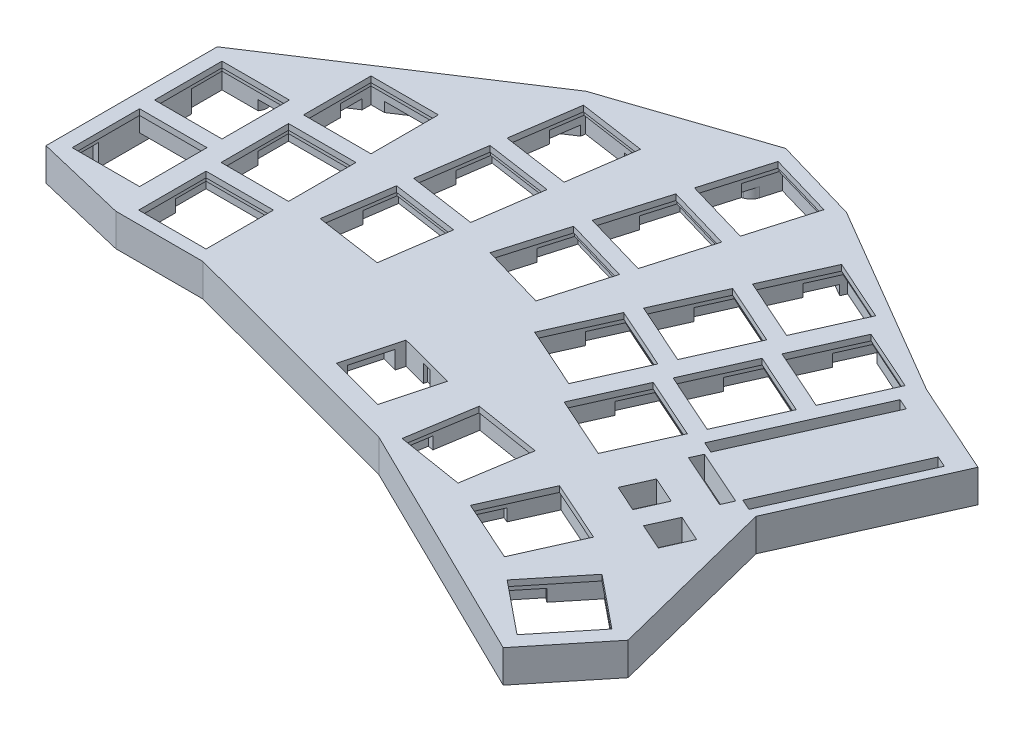
SolidWorks part; units mm, degrees
ref_plane "Front Plane" through (0, 0, 0) normal (0, 0, 1) x (1, 0, 0)
ref_plane "Top Plane" through (0, 0, 0) normal (0, 1, 0) x (1, 0, 0)
ref_plane "Right Plane" through (0, 0, 0) normal (1, 0, 0) x (0, 0, -1)
sketch "Ergogen Drawing" plane through (0, 0, 0) normal (0, 1, 0) x (1, 0, 0)
  line L0 (0.027, 17.9992) -> (18.027, 17.9992)
  line L1 (18.027, 17.9992) -> (18.027, -0.0008)
  line L2 (18.027, -0.0008) -> (0.027, -0.0008)
  line L3 (0.027, -0.0008) -> (0.027, 17.9992)
  line L4 (0.027, 34.9992) -> (18.027, 34.9992)
  line L5 (18.027, 34.9992) -> (18.027, 16.9992)
  line L6 (18.027, 16.9992) -> (0.027, 16.9992)
  line L7 (0.027, 16.9992) -> (0.027, 34.9992)
  line L8 (18.027, 15.9992) -> (36.027, 15.9992)
  line L9 (36.027, 15.9992) -> (36.027, -2.0008)
  line L10 (36.027, -2.0008) -> (18.027, -2.0008)
  line L11 (18.027, -2.0008) -> (18.027, 15.9992)
  line L12 (18.027, 32.9992) -> (36.027, 32.9992)
  line L13 (36.027, 32.9992) -> (36.027, 14.9992)
  line L14 (36.027, 14.9992) -> (18.027, 14.9992)
  line L15 (18.027, 14.9992) -> (18.027, 32.9992)
  line L16 (18.027, 49.9992) -> (36.027, 49.9992)
  line L17 (36.027, 49.9992) -> (36.027, 31.9992)
  line L18 (36.027, 31.9992) -> (18.027, 31.9992)
  line L19 (18.027, 31.9992) -> (18.027, 49.9992)
  line L20 (41.3768, 32.6051) -> (59.3329, 31.3495)
  line L21 (59.3329, 31.3495) -> (58.0773, 13.3933)
  line L22 (58.0773, 13.3933) -> (40.1211, 14.6489)
  line L23 (40.1211, 14.6489) -> (41.3768, 32.6051)
  line L24 (42.5626, 49.5637) -> (60.5188, 48.3081)
  line L25 (60.5188, 48.3081) -> (59.2631, 30.3519)
  line L26 (59.2631, 30.3519) -> (41.307, 31.6075)
  line L27 (41.307, 31.6075) -> (42.5626, 49.5637)
  line L28 (43.7485, 66.5223) -> (61.7046, 65.2667)
  line L29 (61.7046, 65.2667) -> (60.449, 47.3105)
  line L30 (60.449, 47.3105) -> (42.4929, 48.5661)
  line L31 (42.4929, 48.5661) -> (43.7485, 66.5223)
  line L32 (66.0898, 43.7082) -> (83.8507, 40.7838)
  line L33 (83.8507, 40.7838) -> (80.9263, 23.023)
  line L34 (80.9263, 23.023) -> (63.1655, 25.9473)
  line L35 (63.1655, 25.9473) -> (66.0898, 43.7082)
  line L36 (68.8517, 60.4823) -> (86.6126, 57.558)
  line L37 (86.6126, 57.558) -> (83.6882, 39.7971)
  line L38 (83.6882, 39.7971) -> (65.9274, 42.7215)
  line L39 (65.9274, 42.7215) -> (68.8517, 60.4823)
  line L40 (71.6136, 77.2565) -> (89.3745, 74.3321)
  line L41 (89.3745, 74.3321) -> (86.4501, 56.5713)
  line L42 (86.4501, 56.5713) -> (68.6893, 59.4956)
  line L43 (68.6893, 59.4956) -> (71.6136, 77.2565)
  line L44 (88.5581, 32.769) -> (105.9366, 28.0799)
  line L45 (105.9366, 28.0799) -> (101.2475, 10.7014)
  line L46 (101.2475, 10.7014) -> (83.869, 15.3905)
  line L47 (83.869, 15.3905) -> (88.5581, 32.769)
  line L48 (92.9866, 49.182) -> (110.3652, 44.4929)
  line L49 (110.3652, 44.4929) -> (105.6761, 27.1144)
  line L50 (105.6761, 27.1144) -> (88.2976, 31.8035)
  line L51 (88.2976, 31.8035) -> (92.9866, 49.182)
  line L52 (97.4152, 65.595) -> (114.7937, 60.906)
  line L53 (114.7937, 60.906) -> (110.1046, 43.5274)
  line L54 (110.1046, 43.5274) -> (92.7261, 48.2165)
  line L55 (92.7261, 48.2165) -> (97.4152, 65.595)
  line L56 (107.0448, 26.9674) -> (124.0477, 21.0597)
  line L57 (124.0477, 21.0597) -> (118.14, 4.0568)
  line L58 (118.14, 4.0568) -> (101.1371, 9.9645)
  line L59 (101.1371, 9.9645) -> (107.0448, 26.9674)
  line L60 (112.6243, 43.0257) -> (129.6273, 37.118)
  line L61 (129.6273, 37.118) -> (123.7195, 20.1151)
  line L62 (123.7195, 20.1151) -> (106.7166, 26.0228)
  line L63 (106.7166, 26.0228) -> (112.6243, 43.0257)
  line L64 (118.2039, 59.084) -> (135.2068, 53.1763)
  line L65 (135.2068, 53.1763) -> (129.299, 36.1734)
  line L66 (129.299, 36.1734) -> (112.2961, 42.0811)
  line L67 (112.2961, 42.0811) -> (118.2039, 59.084)
  line L68 (95.4197, 6.4051) -> (112.5714, 0.9445)
  line L69 (112.5714, 0.9445) -> (107.1108, -16.2072)
  line L70 (107.1108, -16.2072) -> (89.959, -10.7466)
  line L71 (89.959, -10.7466) -> (95.4197, 6.4051)
  line L72 (116.0129, -0.5249) -> (131.9353, -8.9198)
  line L73 (131.9353, -8.9198) -> (123.5404, -24.8423)
  line L74 (123.5404, -24.8423) -> (107.6179, -16.4473)
  line L75 (107.6179, -16.4473) -> (116.0129, -0.5249)
  line L76 (135.0644, -10.9721) -> (149.2602, -22.0392)
  line L77 (149.2602, -22.0392) -> (138.1931, -36.235)
  line L78 (138.1931, -36.235) -> (123.9973, -25.1679)
  line L79 (123.9973, -25.1679) -> (135.0644, -10.9721)
sketch "Layout Based on OG" plane through (0, 0, 0) normal (0, 1, 0) x (1, 0, 0)
  line L0 (0, 0) -> (0, 17) construction
  line L1 (0, 17) -> (18, 17) construction
  line L2 (18, 17) -> (18, 0) construction
  line L3 (18, 0) -> (0, 0) construction
  line L4 (2.05, 1.55) -> (2.05, 15.45)
  line L5 (2.05, 15.45) -> (15.95, 15.45)
  line L6 (15.95, 15.45) -> (15.95, 1.55)
  line L7 (15.95, 1.55) -> (2.05, 1.55)
  line L8 (109.1798, 58.6066) -> (27, -125.5436) construction
  line L9 (27, 46.7087) -> (27, -125.5436) construction
  line L10 (84.3863, 71.4039) -> (27, -125.5436) construction
  line L11 (54.2678, 62.3831) -> (27, -125.5436) construction
  line L12 (44.7261, 45.0233) -> (58.4821, 43.0274)
  line L13 (2.05, 18.55) -> (15.95, 18.55)
  line L14 (2.05, 18.55) -> (2.05, 32.45)
  line L15 (2.05, 32.45) -> (15.95, 32.45)
  line L16 (15.95, 18.55) -> (15.95, 32.45)
  line L17 (20.05, 31.2587) -> (33.95, 31.2587)
  line L18 (20.05, 31.2587) -> (20.05, 45.1587)
  line L19 (20.05, 45.1587) -> (33.95, 45.1587)
  line L20 (33.95, 31.2587) -> (33.95, 45.1587)
  line L21 (33.95, 28.1587) -> (20.05, 28.1587)
  line L22 (33.95, 28.1587) -> (33.95, 14.2587)
  line L23 (33.95, 14.2587) -> (20.05, 14.2587)
  line L24 (20.05, 28.1587) -> (20.05, 14.2587)
  line L25 (20.05, -2.7413) -> (33.95, -2.7413)
  line L26 (20.05, -2.7413) -> (20.05, 11.1587)
  line L27 (20.05, 11.1587) -> (33.95, 11.1587)
  line L28 (33.95, -2.7413) -> (33.95, 11.1587)
  line L29 (44.7261, 45.0233) -> (42.7302, 31.2674)
  line L30 (58.4821, 43.0274) -> (56.4861, 29.2714)
  line L31 (42.7302, 31.2674) -> (56.4861, 29.2714)
  line L32 (42.285, 28.1995) -> (56.041, 26.2036)
  line L33 (42.285, 28.1995) -> (40.2891, 14.4436)
  line L34 (56.041, 26.2036) -> (54.045, 12.4476)
  line L35 (40.2891, 14.4436) -> (54.045, 12.4476)
  line L36 (47.1672, 61.8472) -> (60.9232, 59.8512)
  line L37 (47.1672, 61.8472) -> (45.1712, 48.0912)
  line L38 (60.9232, 59.8512) -> (58.9272, 46.0953)
  line L39 (45.1712, 48.0912) -> (58.9272, 46.0953)
  line L40 (77.2802, 71.86) -> (90.6252, 67.9716)
  line L41 (77.2802, 71.86) -> (73.3917, 58.515)
  line L42 (90.6252, 67.9716) -> (86.7368, 54.6265)
  line L43 (73.3917, 58.515) -> (86.7368, 54.6265)
  line L44 (85.8695, 51.6503) -> (72.5245, 55.5388)
  line L45 (85.8695, 51.6503) -> (81.9811, 38.3053)
  line L46 (72.5245, 55.5388) -> (68.6361, 42.1937)
  line L47 (81.9811, 38.3053) -> (68.6361, 42.1937)
  line L48 (67.7688, 39.2175) -> (81.1139, 35.329)
  line L49 (67.7688, 39.2175) -> (63.8804, 25.8725)
  line L50 (81.1139, 35.329) -> (77.2254, 21.984)
  line L51 (63.8804, 25.8725) -> (77.2254, 21.984)
  line L52 (102.2015, 60.0235) -> (114.8949, 54.3589)
  line L53 (102.2015, 60.0235) -> (96.5369, 47.3301)
  line L54 (114.8949, 54.3589) -> (109.2302, 41.6655)
  line L55 (96.5369, 47.3301) -> (109.2302, 41.6655)
  line L56 (107.9669, 38.8346) -> (95.2735, 44.4992)
  line L57 (107.9669, 38.8346) -> (102.3023, 26.1412)
  line L58 (95.2735, 44.4992) -> (89.6089, 31.8058)
  line L59 (102.3023, 26.1412) -> (89.6089, 31.8058)
  line L60 (101.039, 23.3103) -> (88.3456, 28.9749)
  line L61 (101.039, 23.3103) -> (95.3744, 10.6169)
  line L62 (88.3456, 28.9749) -> (82.681, 16.2815)
  line L63 (95.3744, 10.6169) -> (82.681, 16.2815)
  line L64 (117.7053, 50.5958) -> (130.3987, 44.9312)
  line L65 (117.7053, 50.5958) -> (112.0407, 37.9024)
  line L66 (130.3987, 44.9312) -> (124.734, 32.2378)
  line L67 (112.0407, 37.9024) -> (124.734, 32.2378)
  line L68 (123.4707, 29.4069) -> (110.7773, 35.0715)
  line L69 (123.4707, 29.4069) -> (117.8061, 16.7135)
  line L70 (110.7773, 35.0715) -> (105.1127, 22.3782)
  line L71 (117.8061, 16.7135) -> (105.1127, 22.3782)
  line L72 (116.5428, 13.8826) -> (103.8494, 19.5473)
  line L73 (116.5428, 13.8826) -> (110.8782, 1.1892)
  line L74 (103.8494, 19.5473) -> (98.1848, 6.8539)
  line L75 (110.8782, 1.1892) -> (98.1848, 6.8539)
  line L76 (90.1692, -2.6429) -> (103.8962, -4.8292)
  line L77 (90.1692, -2.6429) -> (87.9829, -16.3699)
  line L78 (103.8962, -4.8292) -> (101.7099, -18.5562)
  line L79 (87.9829, -16.3699) -> (101.7099, -18.5562)
  line L80 (112.6329, -8.5638) -> (125.3263, -14.2284)
  line L81 (112.6329, -8.5638) -> (106.9683, -21.2572)
  line L82 (125.3263, -14.2284) -> (119.6617, -26.9218)
  line L83 (106.9683, -21.2572) -> (119.6617, -26.9218)
  line L84 (132.8305, -19.9983) -> (143.6253, -28.7552)
  line L85 (132.8305, -19.9983) -> (124.0737, -30.7931)
  line L86 (143.6253, -28.7552) -> (134.8684, -39.55)
  line L87 (124.0737, -30.7931) -> (134.8684, -39.55)
  line L88 (0, 0) -> (0, 34) construction
  line L89 (0, 34) -> (18, 46.7087) construction
  line L90 (18, 46.7087) -> (45.361, 63.6755) construction
  line L91 (45.361, 63.6755) -> (75.7456, 73.9216) construction
  line L92 (75.7456, 73.9216) -> (93.027, 68.8862) construction
  line L93 (93.027, 68.8862) -> (117.3986, 54.9389) construction
  line L94 (117.3986, 54.9389) -> (132.9024, 45.5112) construction
  line L95 (146.1938, -28.843) -> (135.484, -42.0452) construction
  line L96 (135.484, -42.0452) -> (85.7146, -17.5782) construction
  line L97 (0, 0) -> (18, -4.2913) construction
  line L98 (132.9024, 45.5112) -> (119.0465, 14.4627) construction
  line L99 (18, -4.2913) -> (36, -4.2913) construction
  line L100 (36, -4.2913) -> (85.7146, -17.5782) construction
  line L101 (119.0465, 14.4627) -> (137.3104, 6.3121) construction
  line L102 (137.3104, 6.3121) -> (151.1662, 37.3607) construction
  line L103 (151.1662, 37.3607) -> (132.9024, 45.5112) construction
  line L104 (146.1938, -28.843) -> (137.3104, 6.3121) construction
  line L105 (137.3104, 6.3121) -> (151.1662, 37.3607) construction
  line L106 (151.1662, 37.3607) -> (132.9024, 45.5112) construction
  line L107 (119.9597, 14.0551) -> (132.3892, 41.9075)
  line L108 (132.3892, 41.9075) -> (134.6722, 40.8887)
  line L109 (134.6722, 40.8887) -> (122.2427, 13.0363)
  line L110 (122.2427, 13.0363) -> (119.9597, 14.0551)
  line L111 (136.3972, 6.7197) -> (148.8267, 34.5721)
  line L112 (148.8267, 34.5721) -> (146.5437, 35.5909)
  line L113 (146.5437, 35.5909) -> (134.1142, 7.7385)
  line L114 (134.1142, 7.7385) -> (136.3972, 6.7197)
  line L115 (79.4058, -12.7868) -> (67.8127, -9.6883)
  line L116 (67.8127, -9.6883) -> (70.8336, 1.6149)
  line L117 (70.8336, 1.6149) -> (82.4267, -1.4835)
  line L118 (82.4267, -1.4835) -> (79.4058, -12.7868)
  line L119 (97.0327, -3.7361) -> (94.8464, -17.4631) construction
  line L120 (118.9913, -2.8379) -> (121.4364, 2.6412)
  line L121 (121.4364, 2.6412) -> (126.9156, 0.1961)
  line L122 (76.6302, 0.0657) -> (73.6092, -11.2375) construction
  line L123 (126.9156, 0.1961) -> (124.4704, -5.2831)
  line L124 (124.4704, -5.2831) -> (118.9913, -2.8379)
  line L125 (128.4611, -7.064) -> (130.9062, -1.5848)
  line L126 (130.9062, -1.5848) -> (136.3854, -4.03)
  line L127 (136.3854, -4.03) -> (133.9402, -9.5091)
  line L128 (133.9402, -9.5091) -> (128.4611, -7.064)
  line L137 (124.176, 1.4187) -> (121.7308, -4.0605) construction
  line L138 (133.6458, -2.8074) -> (131.2006, -8.2865) construction
  line L139 (126.7317, 7.1456) -> (128.1784, 10.3874) construction
  line L140 (135.0103, 42.8732) -> (147.795, 37.1678) construction
  line L141 (147.795, 37.1678) -> (133.1241, 4.2929) construction
  line L142 (133.1241, 4.2929) -> (120.3393, 9.9982) construction
  line L143 (120.3393, 9.9982) -> (135.0103, 42.8732) construction
  line L144 (120.9512, 9.7252) -> (121.97, 12.0082)
  line L145 (121.97, 12.0082) -> (133.531, 6.8489)
  line L146 (133.531, 6.8489) -> (132.5122, 4.5659)
  line L147 (132.5122, 4.5659) -> (120.9512, 9.7252)
  line L148 (126.9156, 0.1961) -> (140.3735, -5.8097) construction
  line L164 (-1, 34.5181) -> (-1, -0.7896)
  line L165 (-1, -0.7896) -> (17.8824, -5.2913)
  line L166 (17.8824, -5.2913) -> (35.8687, -5.2913)
  line L167 (35.8687, -5.2913) -> (85.3615, -18.5189)
  line L168 (85.3615, -18.5189) -> (135.7583, -43.2944)
  line L169 (135.7583, -43.2944) -> (147.2861, -29.0838)
  line L170 (147.2861, -29.0838) -> (138.3648, 6.2211)
  line L171 (138.3648, 6.2211) -> (152.487, 37.8664)
  line L172 (152.487, 37.8664) -> (133.3678, 46.3986)
  line L173 (133.3678, 46.3986) -> (117.9068, 55.8002) construction
  line L174 (117.9068, 55.8002) -> (93.4207, 69.8131) construction
  line L175 (93.4207, 69.8131) -> (75.7238, 74.9696)
  line L176 (75.7238, 74.9696) -> (44.9321, 64.5862)
  line L177 (44.9321, 64.5862) -> (17.4476, 47.5429) construction
  line L178 (17.4476, 47.5429) -> (-1, 34.5181) construction
  line L179 (-1, 34.5181) -> (44.9321, 64.5862)
  line L180 (133.3678, 46.3986) -> (93.4207, 69.8131)
  circle A0 centre (143.0056, -24.3895) radius 2 construction
  circle A1 centre (143.0056, -24.3895) radius 1
  circle A2 centre (98.5143, -21.642) radius 2 construction
  circle A3 centre (98.5143, -21.642) radius 1
  circle A6 centre (17.05, -2.0087) radius 2 construction
  circle A7 centre (17.05, -2.0087) radius 1
  circle A8 centre (5.901, 35.45) radius 2 construction
  circle A9 centre (5.901, 35.45) radius 1
  circle A10 centre (72.7535, 70.802) radius 2 construction
  circle A11 centre (72.7535, 70.802) radius 1
  circle A12 centre (145.3286, 37.7757) radius 2 construction
  circle A13 centre (145.3286, 37.7757) radius 1
  point P10 (110.8277, 18.1304)
  point P11 (117.7557, 33.6547)
  point P128 (75.1197, -5.5859)
  point P129 (95.9395, -10.5996)
  point P146 (127.7505, 9.4285)
  point P148 (128.1784, 10.3874)
  point P150 (122.9534, -1.3209)
  line B0 (18, 29.7087) -> (18, 46.7087) construction
  line B1 (18, 46.7087) -> (36, 46.7087) construction
  line B2 (36, 46.7087) -> (36, 29.7087) construction
  line B3 (36, 29.7087) -> (18, 29.7087) construction
  line B4 (20.05, 31.2587) -> (20.05, 45.1587) construction
  line B5 (20.05, 45.1587) -> (33.95, 45.1587) construction
  line B6 (33.95, 45.1587) -> (33.95, 31.2587) construction
  line B7 (33.95, 31.2587) -> (20.05, 31.2587) construction
  line B8 (18, 12.7087) -> (18, 29.7087) construction
  line B9 (18, 29.7087) -> (36, 29.7087) construction
  line B10 (36, 29.7087) -> (36, 12.7087) construction
  line B11 (36, 12.7087) -> (18, 12.7087) construction
  line B12 (20.05, 14.2587) -> (20.05, 28.1587) construction
  line B13 (20.05, 28.1587) -> (33.95, 28.1587) construction
  line B14 (33.95, 28.1587) -> (33.95, 14.2587) construction
  line B15 (33.95, 14.2587) -> (20.05, 14.2587) construction
  line B16 (18, -4.2913) -> (18, 12.7087) construction
  line B17 (18, 12.7087) -> (36, 12.7087) construction
  line B18 (36, 12.7087) -> (36, -4.2913) construction
  line B19 (36, -4.2913) -> (18, -4.2913) construction
  line B20 (20.05, -2.7413) -> (20.05, 11.1587) construction
  line B21 (20.05, 11.1587) -> (33.95, 11.1587) construction
  line B22 (33.95, 11.1587) -> (33.95, -2.7413) construction
  line B23 (33.95, -2.7413) -> (20.05, -2.7413) construction
  line B24 (42.9199, 46.8516) -> (45.361, 63.6755) construction
  line B25 (45.361, 63.6755) -> (63.1745, 61.0908) construction
  line B26 (63.1745, 61.0908) -> (60.7334, 44.267) construction
  line B27 (60.7334, 44.267) -> (42.9199, 46.8516) construction
  line B28 (45.1712, 48.0912) -> (47.1672, 61.8472) construction
  line B29 (47.1672, 61.8472) -> (60.9232, 59.8512) construction
  line B30 (60.9232, 59.8512) -> (58.9272, 46.0953) construction
  line B31 (58.9272, 46.0953) -> (45.1712, 48.0912) construction
  line B32 (40.4788, 30.0278) -> (42.9199, 46.8516) construction
  line B33 (42.9199, 46.8516) -> (60.7334, 44.267) construction
  line B34 (60.7334, 44.267) -> (58.2923, 27.4431) construction
  line B35 (58.2923, 27.4431) -> (40.4788, 30.0278) construction
  line B36 (42.7302, 31.2674) -> (44.7261, 45.0233) construction
  line B37 (44.7261, 45.0233) -> (58.4821, 43.0274) construction
  line B38 (58.4821, 43.0274) -> (56.4861, 29.2714) construction
  line B39 (56.4861, 29.2714) -> (42.7302, 31.2674) construction
  line B40 (38.0377, 13.204) -> (40.4788, 30.0278) construction
  line B41 (40.4788, 30.0278) -> (58.2923, 27.4431) construction
  line B42 (58.2923, 27.4431) -> (55.8512, 10.6193) construction
  line B43 (55.8512, 10.6193) -> (38.0377, 13.204) construction
  line B44 (40.2891, 14.4436) -> (42.285, 28.1995) construction
  line B45 (42.285, 28.1995) -> (56.041, 26.2036) construction
  line B46 (56.041, 26.2036) -> (54.045, 12.4476) construction
  line B47 (54.045, 12.4476) -> (40.2891, 14.4436) construction
  line B48 (70.99, 57.6004) -> (75.7456, 73.9216) construction
  line B49 (75.7456, 73.9216) -> (93.027, 68.8862) construction
  line B50 (93.027, 68.8862) -> (88.2713, 52.5649) construction
  line B51 (88.2713, 52.5649) -> (70.99, 57.6004) construction
  line B52 (73.3917, 58.515) -> (77.2802, 71.86) construction
  line B53 (77.2802, 71.86) -> (90.6252, 67.9716) construction
  line B54 (90.6252, 67.9716) -> (86.7368, 54.6265) construction
  line B55 (86.7368, 54.6265) -> (73.3917, 58.515) construction
  line B56 (66.2343, 41.2791) -> (70.99, 57.6004) construction
  line B57 (70.99, 57.6004) -> (88.2713, 52.5649) construction
  line B58 (88.2713, 52.5649) -> (83.5156, 36.2437) construction
  line B59 (83.5156, 36.2437) -> (66.2343, 41.2791) construction
  line B60 (68.6361, 42.1937) -> (72.5245, 55.5388) construction
  line B61 (72.5245, 55.5388) -> (85.8695, 51.6503) construction
  line B62 (85.8695, 51.6503) -> (81.9811, 38.3053) construction
  line B63 (81.9811, 38.3053) -> (68.6361, 42.1937) construction
  line B64 (61.4786, 24.9578) -> (66.2343, 41.2791) construction
  line B65 (66.2343, 41.2791) -> (83.5156, 36.2437) construction
  line B66 (83.5156, 36.2437) -> (78.76, 19.9224) construction
  line B67 (78.76, 19.9224) -> (61.4786, 24.9578) construction
  line B68 (63.8804, 25.8725) -> (67.7688, 39.2175) construction
  line B69 (67.7688, 39.2175) -> (81.1139, 35.329) construction
  line B70 (81.1139, 35.329) -> (77.2254, 21.984) construction
  line B71 (77.2254, 21.984) -> (63.8804, 25.8725) construction
  line B72 (80.1772, 15.7015) -> (87.1052, 31.2258) construction
  line B73 (87.1052, 31.2258) -> (103.5427, 23.8903) construction
  line B74 (103.5427, 23.8903) -> (96.6147, 8.366) construction
  line B75 (96.6147, 8.366) -> (80.1772, 15.7015) construction
  line B76 (82.681, 16.2815) -> (88.3456, 28.9749) construction
  line B77 (88.3456, 28.9749) -> (101.039, 23.3103) construction
  line B78 (101.039, 23.3103) -> (95.3744, 10.6169) construction
  line B79 (95.3744, 10.6169) -> (82.681, 16.2815) construction
  line B80 (87.1052, 31.2258) -> (94.0331, 46.7501) construction
  line B81 (94.0331, 46.7501) -> (110.4706, 39.4146) construction
  line B82 (110.4706, 39.4146) -> (103.5427, 23.8903) construction
  line B83 (103.5427, 23.8903) -> (87.1052, 31.2258) construction
  line B84 (89.6089, 31.8058) -> (95.2735, 44.4992) construction
  line B85 (95.2735, 44.4992) -> (107.9669, 38.8346) construction
  line B86 (107.9669, 38.8346) -> (102.3023, 26.1412) construction
  line B87 (102.3023, 26.1412) -> (89.6089, 31.8058) construction
  line B88 (94.0331, 46.7501) -> (100.9611, 62.2744) construction
  line B89 (100.9611, 62.2744) -> (117.3986, 54.9389) construction
  line B90 (117.3986, 54.9389) -> (110.4706, 39.4146) construction
  line B91 (110.4706, 39.4146) -> (94.0331, 46.7501) construction
  line B92 (96.5369, 47.3301) -> (102.2015, 60.0235) construction
  line B93 (102.2015, 60.0235) -> (114.8949, 54.3589) construction
  line B94 (114.8949, 54.3589) -> (109.2302, 41.6655) construction
  line B95 (109.2302, 41.6655) -> (96.5369, 47.3301) construction
  line B96 (109.5369, 37.3224) -> (116.4649, 52.8467) construction
  line B97 (116.4649, 52.8467) -> (132.9024, 45.5112) construction
  line B98 (132.9024, 45.5112) -> (125.9744, 29.9869) construction
  line B99 (125.9744, 29.9869) -> (109.5369, 37.3224) construction
  line B100 (112.0407, 37.9024) -> (117.7053, 50.5958) construction
  line B101 (117.7053, 50.5958) -> (130.3987, 44.9312) construction
  line B102 (130.3987, 44.9312) -> (124.734, 32.2378) construction
  line B103 (124.734, 32.2378) -> (112.0407, 37.9024) construction
  line B104 (102.609, 21.7981) -> (109.5369, 37.3224) construction
  line B105 (109.5369, 37.3224) -> (125.9744, 29.9869) construction
  line B106 (125.9744, 29.9869) -> (119.0465, 14.4627) construction
  line B107 (119.0465, 14.4627) -> (102.609, 21.7981) construction
  line B108 (105.1127, 22.3782) -> (110.7773, 35.0715) construction
  line B109 (110.7773, 35.0715) -> (123.4707, 29.4069) construction
  line B110 (123.4707, 29.4069) -> (117.8061, 16.7135) construction
  line B111 (117.8061, 16.7135) -> (105.1127, 22.3782) construction
  line B112 (95.6811, 6.2738) -> (102.609, 21.7981) construction
  line B113 (102.609, 21.7981) -> (119.0465, 14.4627) construction
  line B114 (119.0465, 14.4627) -> (112.1185, -1.0616) construction
  line B115 (112.1185, -1.0616) -> (95.6811, 6.2738) construction
  line B116 (98.1848, 6.8539) -> (103.8494, 19.5473) construction
  line B117 (103.8494, 19.5473) -> (116.5428, 13.8826) construction
  line B118 (116.5428, 13.8826) -> (110.8782, 1.1892) construction
  line B119 (110.8782, 1.1892) -> (98.1848, 6.8539) construction
  line B120 (104.4646, -21.8372) -> (111.3925, -6.3129) construction
  line B121 (111.3925, -6.3129) -> (127.83, -13.6484) construction
  line B122 (127.83, -13.6484) -> (120.9021, -29.1727) construction
  line B123 (120.9021, -29.1727) -> (104.4646, -21.8372) construction
  line B124 (106.9683, -21.2572) -> (112.6329, -8.5638) construction
  line B125 (112.6329, -8.5638) -> (125.3263, -14.2284) construction
  line B126 (125.3263, -14.2284) -> (119.6617, -26.9218) construction
  line B127 (119.6617, -26.9218) -> (106.9683, -21.2572) construction
  line B128 (85.7146, -17.5782) -> (88.3885, -0.7898) construction
  line B129 (88.3885, -0.7898) -> (106.1645, -3.621) construction
  line B130 (106.1645, -3.621) -> (103.4906, -20.4094) construction
  line B131 (103.4906, -20.4094) -> (85.7146, -17.5782) construction
  line B132 (87.9829, -16.3699) -> (90.1692, -2.6429) construction
  line B133 (90.1692, -2.6429) -> (103.8962, -4.8292) construction
  line B134 (103.8962, -4.8292) -> (101.7099, -18.5562) construction
  line B135 (101.7099, -18.5562) -> (87.9829, -16.3699) construction
  line B136 (121.5051, -30.7054) -> (132.215, -17.5031) construction
  line B137 (132.215, -17.5031) -> (146.1938, -28.843) construction
  line B138 (146.1938, -28.843) -> (135.484, -42.0452) construction
  line B139 (135.484, -42.0452) -> (121.5051, -30.7054) construction
  line B140 (124.0737, -30.7931) -> (132.8305, -19.9983) construction
  line B141 (132.8305, -19.9983) -> (143.6253, -28.7552) construction
  line B142 (143.6253, -28.7552) -> (134.8684, -39.55) construction
  line B143 (134.8684, -39.55) -> (124.0737, -30.7931) construction
  line B144 (0, 17) -> (0, 34) construction
  line B145 (0, 34) -> (18, 34) construction
  line B146 (18, 34) -> (18, 17) construction
  line B147 (18, 17) -> (0, 17) construction
  line B148 (2.05, 18.55) -> (2.05, 32.45) construction
  line B149 (2.05, 32.45) -> (15.95, 32.45) construction
  line B150 (15.95, 32.45) -> (15.95, 18.55) construction
  line B151 (15.95, 18.55) -> (2.05, 18.55) construction
  dimension "D46" = 4
  dimension "D47" = 2
  dimension "D48" = 3
  dimension "D52" = 4
  dimension "D53" = 2
  dimension "D54" = 4
  dimension "D55" = 2
  dimension "D57" = 4
  dimension "D58" = 2
  dimension "D60" = 4
  dimension "D61" = 2
  dimension "D63" = 4
  dimension "D64" = 2
  dimension "D51" = 3
  dimension "D1" = 18
  dimension "D2" = 17
  dimension "D3" = 13.9
  dimension "D4" = 13.9
  dimension "D5" = 2.05
  dimension "D6" = 1.55
  dimension "D7" = 205.1378
  dimension "D8" = 201.6553
  dimension "D9" = 189.8947
  dimension "D10" = 8.256
  dimension "D11" = 15
  dimension "D12" = 15
  dimension "D13" = 1.4278
  dimension "D14" = 0.974
  dimension "D15" = 1.5327
  dimension "D16" = 0.6031
  dimension "D17" = 5.9541
  dimension "D18" = 2.5593
  dimension "D19" = 7.805
  dimension "D20" = 7.989
  dimension "D21" = 172.2524
  dimension "D22" = 2.2911
  dimension "D23" = 4.2913
  dimension "D24" = 34
  dimension "D25" = 20
  dimension "D26" = 30.5
  dimension "D27" = 2.5
  dimension "D28" = 1
  dimension "D29" = 2.5
  dimension "D30" = 30.5
  dimension "D31" = 18
  dimension "D32" = 11.7
  dimension "D33" = 12
  dimension "D34" = 3
  dimension "D35" = 21.415
  dimension "D36" = 6
  dimension "D37" = 6
  dimension "D38" = 6
  dimension "D39" = 6
  dimension "D40" = 14
  dimension "D41" = 36
  dimension "D42" = 12.66
  dimension "D43" = 2.5
  dimension "D44" = 9.27
  dimension "D45" = 4.37
  dimension "D49" = 3
  dimension "D50" = 3
  dimension "D56" = 3
  dimension "D59" = 3
  dimension "D62" = 3
  dimension "D65" = 3
  dimension "D66" = 3
  dimension "D67" = 1
  dimension "D68" = 1
  dimension "D69" = 1
  dimension "D70" = 1
  dimension "D71" = 1
  dimension "D72" = 1
  dimension "D73" = 1
  dimension "D74" = 1
  dimension "D75" = 1
  dimension "D76" = 1
  dimension "D77" = 1
  dimension "D78" = 1
  dimension "D79" = 1
  dimension "D80" = 1
  dimension "D81" = 1
sketch_block_instance "Block-ChocSwitchCutout-3"
sketch_block "Block-ChocSwitchCutout" parameters "D1"=18, "D2"=17, "D3"=13.9, "D4"=13.9, "D5"=2.05, "D6"=1.55
sketch_block_instance "Block-ChocSwitchCutout-4"
sketch_block_instance "Block-ChocSwitchCutout-5"
sketch_block_instance "Block-ChocSwitchCutout-6"
sketch_block_instance "Block-ChocSwitchCutout-7"
sketch_block_instance "Block-ChocSwitchCutout-8"
sketch_block_instance "Block-ChocSwitchCutout-9"
sketch_block_instance "Block-ChocSwitchCutout-10"
sketch_block_instance "Block-ChocSwitchCutout-11"
sketch_block_instance "Block-ChocSwitchCutout-20"
sketch_block_instance "Block-ChocSwitchCutout-23"
sketch_block_instance "Block-ChocSwitchCutout-24"
sketch_block_instance "Block-ChocSwitchCutout-27"
sketch_block_instance "Block-ChocSwitchCutout-28"
sketch_block_instance "Block-ChocSwitchCutout-29"
sketch_block_instance "Block-ChocSwitchCutout-32"
sketch_block_instance "Block-ChocSwitchCutout-33"
sketch_block_instance "Block-ChocSwitchCutout-34"
sketch_block_instance "Block-ChocSwitchCutout-37"
other "AlignGroup1"
extrude "Top Plate" add sketch "Layout Based on OG" along normal blind 1.2 contours L105 L106 L94 L93 L92 L91 L90 L89 L88 L97 L99 L100 L96 L95 L104 L73 L75 L74 L72 L69 L71 L70 L68 L61 L63 L62 L60 L57 L59 L58 L56 L45 L47 L46 L44 L6 L7 L4 L5 L16 L13 L14 L15 | A9 | A7 | A3 | A1 | A13 | A11 region at (81.2217, 0, -18.9178) region at (143.0056, 0, 24.3895) region at (98.5143, 0, 21.642) region at (17.05, 0, 2.0087) region at (5.901, 0, -35.45) region at (72.7535, 0, -70.802) region at (145.3286, 0, -37.7757)
sketch "Sketch1" plane through (0, 0, 0) normal (0, -1, 0) x (1, 0, 0)
  line L0 (124.9363, -31.7095) -> (130.927, -45.1335)
  line L1 (130.927, -45.1335) -> (117.503, -51.1241)
  line L2 (117.503, -51.1241) -> (111.5124, -37.7002)
  line L3 (111.5124, -37.7002) -> (124.9363, -31.7095)
  line L4 (118.0084, -16.1852) -> (123.999, -29.6092)
  line L5 (117.7053, -50.5958) -> (130.3987, -44.9312) construction
  line L6 (123.999, -29.6092) -> (110.5751, -35.5998)
  line L7 (117.7053, -50.5958) -> (112.0407, -37.9024) construction
  line L8 (110.5751, -35.5998) -> (104.5844, -22.1759)
  line L9 (104.5844, -22.1759) -> (118.0084, -16.1852)
  line L10 (123.4707, -29.4069) -> (117.8061, -16.7135) construction
  line L11 (111.0804, -0.661) -> (117.0711, -14.0849)
  line L12 (117.8061, -16.7135) -> (105.1127, -22.3782) construction
  line L13 (117.0711, -14.0849) -> (103.6471, -20.0755)
  line L14 (103.6471, -20.0755) -> (97.6565, -6.6516)
  line L15 (97.6565, -6.6516) -> (111.0804, -0.661)
  line L16 (103.8494, -19.5473) -> (98.1848, -6.8539) construction
  line L17 (110.8782, -1.1892) -> (98.1848, -6.8539) construction
  line L18 (95.5766, -10.0886) -> (101.5673, -23.5126)
  line L19 (101.5673, -23.5126) -> (88.1433, -29.5032)
  line L20 (88.1433, -29.5032) -> (82.1527, -16.0793)
  line L21 (82.1527, -16.0793) -> (95.5766, -10.0886)
  line L22 (101.039, -23.3103) -> (88.3456, -28.9749) construction
  line L23 (101.039, -23.3103) -> (95.3744, -10.6169) construction
  line L24 (102.5046, -25.6129) -> (108.4952, -39.0369)
  line L25 (108.4952, -39.0369) -> (95.0713, -45.0275)
  line L26 (95.0713, -45.0275) -> (89.0806, -31.6036)
  line L27 (89.0806, -31.6036) -> (102.5046, -25.6129)
  line L28 (102.3023, -26.1412) -> (89.6089, -31.8058) construction
  line L29 (95.2735, -44.4992) -> (89.6089, -31.8058) construction
  line L30 (109.4325, -41.1372) -> (115.4231, -54.5612)
  line L31 (115.4231, -54.5612) -> (101.9992, -60.5518)
  line L32 (101.9992, -60.5518) -> (96.0086, -47.1279)
  line L33 (96.0086, -47.1279) -> (109.4325, -41.1372)
  line L34 (102.2015, -60.0235) -> (114.8949, -54.3589) construction
  line L35 (114.8949, -54.3589) -> (109.2302, -41.6655) construction
  line L36 (119.864, 27.4501) -> (125.8546, 14.0261)
  line L37 (125.8546, 14.0261) -> (112.4307, 8.0355)
  line L38 (112.4307, 8.0355) -> (106.44, 21.4594)
  line L39 (106.44, 21.4594) -> (119.864, 27.4501)
  line L40 (125.3263, 14.2284) -> (119.6617, 26.9218) construction
  line L41 (106.9683, 21.2572) -> (119.6617, 26.9218) construction
  line L42 (144.1879, 28.6966) -> (134.9271, 40.1126)
  line L43 (134.9271, 40.1126) -> (123.511, 30.8517)
  line L44 (123.511, 30.8517) -> (132.7719, 19.4357)
  line L45 (132.7719, 19.4357) -> (144.1879, 28.6966)
  line L46 (143.6253, 28.7552) -> (134.8684, 39.55) construction
  line L47 (132.8305, 19.9983) -> (143.6253, 28.7552) construction
  line L48 (132.8305, 19.9983) -> (124.0737, 30.7931) construction
  line L49 (104.3541, 4.4971) -> (102.042, 19.0142)
  line L50 (102.042, 19.0142) -> (87.5249, 16.702)
  line L51 (87.5249, 16.702) -> (89.8371, 2.185)
  line L52 (89.8371, 2.185) -> (104.3541, 4.4971)
  line L61 (86.3655, -51.9224) -> (82.2532, -37.8093)
  line L62 (103.8962, 4.8292) -> (101.7099, 18.5562) construction
  line L63 (82.2532, -37.8093) -> (68.1401, -41.9216)
  line L64 (87.9829, 16.3699) -> (101.7099, 18.5562) construction
  line L65 (91.1211, -68.2437) -> (87.0089, -54.1306)
  line L66 (87.0089, -54.1306) -> (72.8958, -58.2429)
  line L67 (72.8958, -58.2429) -> (77.008, -72.3559)
  line L68 (77.008, -72.3559) -> (91.1211, -68.2437)
  line L69 (61.3764, -60.1896) -> (59.2656, -45.642)
  line L70 (59.2656, -45.642) -> (44.718, -47.7528)
  line L71 (44.718, -47.7528) -> (46.8288, -62.3005)
  line L72 (46.8288, -62.3005) -> (61.3764, -60.1896)
  line L73 (34.35, -45.5587) -> (34.35, -30.8587)
  line L74 (34.35, -30.8587) -> (19.65, -30.8587)
  line L75 (19.65, -30.8587) -> (19.65, -45.5587)
  line L76 (19.65, -45.5587) -> (34.35, -45.5587)
  line L77 (90.6252, -67.9716) -> (86.7368, -54.6265) construction
  line L78 (47.1672, -61.8472) -> (45.1712, -48.0912) construction
  line L79 (33.95, -31.2587) -> (33.95, -45.1587) construction
  line L80 (73.3917, -58.515) -> (86.7368, -54.6265) construction
  line L81 (60.9232, -59.8512) -> (58.9272, -46.0953) construction
  line L82 (45.1712, -48.0912) -> (58.9272, -46.0953) construction
  line L83 (68.1401, -41.9216) -> (72.2524, -56.0347)
  line L84 (20.05, -31.2587) -> (33.95, -31.2587) construction
  line L85 (72.2524, -56.0347) -> (86.3655, -51.9224)
  line L86 (85.8695, -51.6503) -> (81.9811, -38.3053) construction
  line L87 (81.9811, -38.3053) -> (68.6361, -42.1937) construction
  line L88 (81.6098, -35.6012) -> (77.4976, -21.4881)
  line L89 (77.4976, -21.4881) -> (63.3845, -25.6003)
  line L90 (63.3845, -25.6003) -> (67.4967, -39.7134)
  line L91 (67.4967, -39.7134) -> (81.6098, -35.6012)
  line L92 (81.1139, -35.329) -> (77.2254, -21.984) construction
  line L93 (63.8804, -25.8725) -> (77.2254, -21.984) construction
  line L94 (58.9353, -43.3658) -> (56.8245, -28.8181)
  line L95 (56.8245, -28.8181) -> (42.2769, -30.929)
  line L96 (42.2769, -30.929) -> (44.3877, -45.4766)
  line L97 (44.3877, -45.4766) -> (58.9353, -43.3658)
  line L98 (58.4821, -43.0274) -> (56.4861, -29.2714) construction
  line L99 (42.7302, -31.2674) -> (56.4861, -29.2714) construction
  line L100 (56.4943, -26.542) -> (54.3834, -11.9943)
  line L101 (54.3834, -11.9943) -> (39.8358, -14.1052)
  line L102 (39.8358, -14.1052) -> (41.9466, -28.6528)
  line L103 (41.9466, -28.6528) -> (56.4943, -26.542)
  line L104 (56.041, -26.2036) -> (54.045, -12.4476) construction
  line L105 (40.2891, -14.4436) -> (54.045, -12.4476) construction
  line L106 (34.35, -28.5587) -> (34.35, -13.8587)
  line L107 (34.35, -13.8587) -> (19.65, -13.8587)
  line L108 (19.65, -13.8587) -> (19.65, -28.5587)
  line L109 (19.65, -28.5587) -> (34.35, -28.5587)
  line L110 (33.95, -28.1587) -> (33.95, -14.2587) construction
  line L111 (33.95, -14.2587) -> (20.05, -14.2587) construction
  line L112 (34.35, -11.5587) -> (34.35, 3.1413)
  line L113 (34.35, 3.1413) -> (19.65, 3.1413)
  line L114 (19.65, 3.1413) -> (19.65, -11.5587)
  line L115 (19.65, -11.5587) -> (34.35, -11.5587)
  line L116 (20.05, 2.7413) -> (33.95, 2.7413) construction
  line L117 (20.05, 2.7413) -> (20.05, -11.1587) construction
  line L118 (16.35, -15.85) -> (16.35, -1.15)
  line L119 (16.35, -1.15) -> (1.65, -1.15)
  line L120 (1.65, -1.15) -> (1.65, -15.85)
  line L121 (1.65, -15.85) -> (16.35, -15.85)
  line L122 (2.05, -1.55) -> (2.05, -15.45) construction
  line L123 (15.95, -1.55) -> (2.05, -1.55) construction
  line L124 (16.35, -32.85) -> (16.35, -18.15)
  line L125 (16.35, -18.15) -> (1.65, -18.15)
  line L126 (1.65, -18.15) -> (1.65, -32.85)
  line L127 (1.65, -32.85) -> (16.35, -32.85)
  line L128 (2.05, -18.55) -> (2.05, -32.45) construction
  line L129 (2.05, -18.55) -> (15.95, -18.55) construction
  dimension "D1" = 14.7
  dimension "D2" = 14.7
  dimension "D3" = 0.4
  dimension "D4" = 0.4
  dimension "D5" = 14.7
  dimension "D6" = 14.7
  dimension "D7" = 0.4
  dimension "D8" = 0.4
  dimension "D9" = 14.7
  dimension "D10" = 14.7
  dimension "D11" = 0.4
  dimension "D12" = 0.4
  dimension "D13" = 14.7
  dimension "D14" = 14.7
  dimension "D15" = 0.4
  dimension "D16" = 0.4
  dimension "D17" = 14.7
  dimension "D18" = 14.7
  dimension "D19" = 0.4
  dimension "D20" = 0.4
  dimension "D21" = 14.7
  dimension "D22" = 0.4
  dimension "D23" = 0.4
  dimension "D24" = 14.7
  dimension "D25" = 14.7
  dimension "D26" = 14.7
  dimension "D27" = 0.4
  dimension "D28" = 0.4
  dimension "D29" = 14.7
  dimension "D30" = 14.7
  dimension "D31" = 0.4
  dimension "D32" = 0.4
  dimension "D33" = 14.7
  dimension "D34" = 14.7
  dimension "D35" = 0.4
  dimension "D36" = 0.4
  dimension "D37" = 0.4
  dimension "D38" = 0.4
  dimension "D39" = 14.7
  dimension "D40" = 14.7
  dimension "D41" = 0.4
  dimension "D42" = 0.4
  dimension "D43" = 14.7
  dimension "D44" = 14.7
  dimension "D45" = 14.7
  dimension "D46" = 0.4
  dimension "D47" = 0.4
  dimension "D48" = 14.7
  dimension "D49" = 14.7
  dimension "D50" = 14.7
  dimension "D51" = 0.4
  dimension "D52" = 0.4
  dimension "D53" = 14.7
  dimension "D54" = 14.7
  dimension "D55" = 0.4
  dimension "D56" = 0.4
  dimension "D57" = 14.7
  dimension "D58" = 14.7
  dimension "D59" = 0.4
  dimension "D60" = 0.4
  dimension "D61" = 14.7
  dimension "D62" = 14.7
  dimension "D63" = 0.4
  dimension "D64" = 0.4
  dimension "D65" = 14.7
  dimension "D66" = 14.7
  dimension "D67" = 0.4
  dimension "D68" = 0.4
  dimension "D69" = 14.7
  dimension "D70" = 14.7
  dimension "D71" = 0.4
  dimension "D72" = 0.4
  dimension "D73" = 14.7
  dimension "D74" = 14.7
  dimension "D75" = 0.4
  dimension "D76" = 0.4
  dimension "D77" = 14.7
  dimension "D78" = 14.7
  dimension "D79" = 0.4
  dimension "D80" = 0.4
extrude "Boss-Extrude2" add sketch "Layout Based on OG<7>" against normal blind 5.5 contours L172 L180 L175 L176 L179 L164 L165 L166 L167 L168 L169 L170 L171 A13 A11 A9 A7 A3 A1 L146 L147 L144 L145 L127 L128 L125 L126 L123 L124 L120 L121 L117 L118 L115 L116 L109 L110 L107 L108 region at (81.2217, 0, -18.9178)
sketch "Layout Based on OG<7>" plane through (0, 0, 0) normal (0, 1, 0) x (1, 0, 0) same geometry as "Layout Based on OG"
extrude "Cut-Extrude1" cut sketch "Sketch1" along normal blind 5.5
sketch "Sketch4" plane through (0, -5.5, 0) normal (0, -1, 0) x (1, 0, 0)
  line L0 (74.3817, 12.2203) -> (77.7899, -0.5321)
  line L1 (77.7899, -0.5321) -> (75.8577, -1.0485)
  line L2 (75.8577, -1.0485) -> (72.4495, 11.7039)
  line L3 (72.4495, 11.7039) -> (74.3817, 12.2203)
  line L4 (67.8127, 9.6883) -> (70.8336, -1.6149) construction
  line L6 (79.4058, 12.7868) -> (67.8127, 9.6883) construction
  line L8 (82.4267, 1.4835) -> (79.4058, 12.7868) construction
  line L9 (83.0232, 11.8386) -> (85.0888, 4.1099)
  line L10 (85.0888, 4.1099) -> (76.394, 1.7861)
  line L11 (76.394, 1.7861) -> (67.2162, -0.6668)
  line L12 (67.2162, -0.6668) -> (65.1505, 7.0619)
  line L14 (83.0232, 11.8386) -> (74.3284, 9.5148)
  line L15 (74.3284, 9.5148) -> (65.1505, 7.0619)
  dimension "D1" = 2
  dimension "D2" = 13.2
  dimension "D3" = 0.75
  dimension "D4" = 5
  dimension "D5" = 9
  dimension "D6" = 9.5
  dimension "D7" = 3.25
  dimension "D8" = 8
  dimension "D9" = 1.85
  dimension "D10" = 9
extrude "Cut-Extrude2" cut sketch "Sketch4" against normal blind 5.7 contours L9 L14 L0 L10 | L2 L15 L12 L11 | L10 L11 L2 L1 L0 | L15 L14 L0 L3 L2 region at (73.7512, -5.5, 10.7062) region at (80.0709, -5.5, 6.9092) region at (76.4882, -5.5, 0.4656) region at (70.1685, -5.5, 4.2626)
sketch "Sketch5" plane through (0, -5.5, 0) normal (0, -1, 0) x (1, 0, 0)
  line L0 (90.4768, -61.9215) -> (92.5469, -69.0261)
  line L1 (92.5469, -69.0261) -> (76.2257, -73.7817)
  line L2 (76.2257, -73.7817) -> (74.1556, -66.6772)
  line L3 (74.1556, -66.6772) -> (90.4768, -61.9215)
  line L4 (91.1211, -68.2437) -> (87.0089, -54.1306) construction
  line L5 (80.9655, -29.279) -> (83.0356, -36.3835)
  line L6 (83.0356, -36.3835) -> (66.7143, -41.1392)
  line L7 (66.7143, -41.1392) -> (64.6442, -34.0347)
  line L8 (64.6442, -34.0347) -> (80.9655, -29.279)
  line L9 (72.2524, -56.0347) -> (86.3655, -51.9224) construction
  line L10 (77.008, -72.3559) -> (91.1211, -68.2437) construction
  line L11 (85.7211, -45.6003) -> (87.7913, -52.7048)
  line L12 (87.7913, -52.7048) -> (71.47, -57.4605)
  line L13 (71.47, -57.4605) -> (69.3999, -50.3559)
  line L14 (69.3999, -50.3559) -> (85.7211, -45.6003)
  line L15 (68.1401, -41.9216) -> (72.2524, -56.0347) construction
  line L16 (81.6098, -35.6012) -> (77.4976, -21.4881) construction
  line L17 (67.4967, -39.7134) -> (81.6098, -35.6012) construction
  line L18 (113.9263, -48.385) -> (116.942, -55.1427)
  line L19 (116.942, -55.1427) -> (101.4177, -62.0706)
  line L20 (101.4177, -62.0706) -> (98.402, -55.313)
  line L21 (98.402, -55.313) -> (113.9263, -48.385)
  line L22 (96.0086, -47.1279) -> (101.9992, -60.5518) construction
  line L23 (106.9983, -32.8608) -> (110.014, -39.6184)
  line L24 (110.014, -39.6184) -> (94.4897, -46.5463)
  line L25 (94.4897, -46.5463) -> (91.474, -39.7887)
  line L26 (91.474, -39.7887) -> (106.9983, -32.8608)
  line L27 (100.0704, -17.3365) -> (103.0861, -24.0941)
  line L28 (103.0861, -24.0941) -> (87.5618, -31.022)
  line L29 (87.5618, -31.022) -> (84.5461, -24.2644)
  line L30 (84.5461, -24.2644) -> (100.0704, -17.3365)
  line L31 (115.5742, -7.9088) -> (118.5899, -14.6664)
  line L32 (118.5899, -14.6664) -> (103.0656, -21.5944)
  line L33 (103.0656, -21.5944) -> (100.0499, -14.8367)
  line L34 (100.0499, -14.8367) -> (115.5742, -7.9088)
  line L35 (122.5021, -23.4331) -> (125.5178, -30.1907)
  line L36 (125.5178, -30.1907) -> (109.9935, -37.1187)
  line L37 (109.9935, -37.1187) -> (106.9778, -30.361)
  line L38 (106.9778, -30.361) -> (122.5021, -23.4331)
  line L39 (129.4301, -38.9574) -> (132.4458, -45.715)
  line L40 (132.4458, -45.715) -> (116.9215, -52.6429)
  line L41 (116.9215, -52.6429) -> (113.9058, -45.8853)
  line L42 (113.9058, -45.8853) -> (129.4301, -38.9574)
  line L43 (130.927, -45.1335) -> (124.9363, -31.7095) construction
  line L44 (117.503, -51.1241) -> (130.927, -45.1335) construction
  line L45 (115.4231, -54.5612) -> (109.4325, -41.1372) construction
  line L46 (101.9992, -60.5518) -> (115.4231, -54.5612) construction
  line L47 (89.0806, -31.6036) -> (95.0713, -45.0275) construction
  line L48 (95.0713, -45.0275) -> (108.4952, -39.0369) construction
  line L49 (88.1433, -29.5032) -> (101.5673, -23.5126) construction
  line L50 (101.5673, -23.5126) -> (95.5766, -10.0886) construction
  line L51 (117.0711, -14.0849) -> (111.0804, -0.661) construction
  line L52 (103.6471, -20.0755) -> (117.0711, -14.0849) construction
  line L53 (123.999, -29.6092) -> (118.0084, -16.1852) construction
  line L54 (110.5751, -35.5998) -> (123.999, -29.6092) construction
  line L55 (61.6171, -53.8393) -> (62.6797, -61.1626)
  line L56 (62.6797, -61.1626) -> (45.8558, -63.6037)
  line L57 (45.8558, -63.6037) -> (44.7932, -56.2804)
  line L58 (44.7932, -56.2804) -> (61.6171, -53.8393)
  line L59 (61.3764, -60.1896) -> (59.2656, -45.642) construction
  line L60 (59.176, -37.0154) -> (60.2386, -44.3387)
  line L61 (60.2386, -44.3387) -> (43.4147, -46.7798)
  line L62 (43.4147, -46.7798) -> (42.3521, -39.4565)
  line L63 (42.3521, -39.4565) -> (59.176, -37.0154)
  line L64 (56.7349, -20.1916) -> (57.7975, -27.5149)
  line L65 (57.7975, -27.5149) -> (40.9736, -29.956)
  line L66 (40.9736, -29.956) -> (39.911, -22.6327)
  line L67 (39.911, -22.6327) -> (56.7349, -20.1916)
  line L68 (35.5, -39.3087) -> (35.5, -46.7087)
  line L69 (35.5, -46.7087) -> (18.5, -46.7087)
  line L70 (18.5, -46.7087) -> (18.5, -39.3087)
  line L71 (18.5, -39.3087) -> (35.5, -39.3087)
  line L72 (34.35, -45.5587) -> (34.35, -30.8587) construction
  line L73 (35.5, -22.3087) -> (35.5, -29.7087)
  line L74 (35.5, -29.7087) -> (18.5, -29.7087)
  line L75 (18.5, -29.7087) -> (18.5, -22.3087)
  line L76 (18.5, -22.3087) -> (35.5, -22.3087)
  line L77 (17.5, -26.6) -> (17.5, -34)
  line L78 (17.5, -34) -> (0.5, -34)
  line L79 (0.5, -34) -> (0.5, -26.6)
  line L80 (0.5, -26.6) -> (17.5, -26.6)
  line L81 (17.5, 0) -> (17.5, -7.4)
  line L82 (17.5, -7.4) -> (0.5, -7.4)
  line L83 (0.5, -7.4) -> (0.5, 0)
  line L84 (0.5, 0) -> (17.5, 0)
  line L85 (35.5, -5.3087) -> (35.5, -12.7087)
  line L86 (35.5, -12.7087) -> (18.5, -12.7087)
  line L87 (18.5, -12.7087) -> (18.5, -5.3087)
  line L88 (18.5, -5.3087) -> (35.5, -5.3087)
  line L89 (46.8288, -62.3005) -> (61.3764, -60.1896) construction
  line L90 (58.9353, -43.3658) -> (56.8245, -28.8181) construction
  line L91 (44.3877, -45.4766) -> (58.9353, -43.3658) construction
  line L92 (41.9466, -28.6528) -> (56.4943, -26.542) construction
  line L93 (39.8358, -14.1052) -> (41.9466, -28.6528) construction
  line L94 (19.65, -45.5587) -> (34.35, -45.5587) construction
  line L95 (19.65, -30.8587) -> (19.65, -45.5587) construction
  line L96 (19.65, -28.5587) -> (34.35, -28.5587) construction
  line L97 (34.35, -28.5587) -> (34.35, -13.8587) construction
  line L98 (19.65, -11.5587) -> (34.35, -11.5587) construction
  line L99 (19.65, 3.1413) -> (19.65, -11.5587) construction
  line L101 (1.65, -1.15) -> (1.65, -15.85) construction
  line L102 (1.65, -32.85) -> (16.35, -32.85) construction
  line L103 (1.65, -18.15) -> (1.65, -32.85) construction
  line L104 (120.4455, 28.9689) -> (123.4612, 22.2113)
  line L105 (123.4612, 22.2113) -> (107.9369, 15.2833)
  line L106 (107.9369, 15.2833) -> (104.9212, 22.0409)
  line L107 (104.9212, 22.0409) -> (120.4455, 28.9689)
  line L108 (102.9968, 20.3307) -> (104.1607, 13.0228)
  line L109 (104.1607, 13.0228) -> (87.3723, 10.3489)
  line L110 (87.3723, 10.3489) -> (86.2084, 17.6568)
  line L111 (86.2084, 17.6568) -> (102.9968, 20.3307)
  line L112 (135.0957, 41.7302) -> (139.7576, 35.9834)
  line L113 (139.7576, 35.9834) -> (126.5554, 25.2735)
  line L114 (126.5554, 25.2735) -> (121.8934, 31.0203)
  line L115 (121.8934, 31.0203) -> (135.0957, 41.7302)
  line L116 (87.5249, 16.702) -> (89.8371, 2.185) construction
  line L117 (123.511, 30.8517) -> (132.7719, 19.4357) construction
  line L118 (106.44, 21.4594) -> (112.4307, 8.0355) construction
  line L119 (102.042, 19.0142) -> (87.5249, 16.702) construction
  line L120 (119.864, 27.4501) -> (106.44, 21.4594) construction
  line L121 (134.9271, 40.1126) -> (123.511, 30.8517) construction
  line L122 (16.35, -1.15) -> (1.65, -1.15) construction
  point P156 (106.429, 18.6621)
  dimension "D1" = 17
  dimension "D2" = 7.4
  dimension "D3" = 1.15
  dimension "D4" = 1.15
  dimension "D5" = 17
  dimension "D6" = 7.4
  dimension "D7" = 17
  dimension "D8" = 7.4
  dimension "D9" = 1.15
  dimension "D10" = 1.15
  dimension "D11" = 1.15
  dimension "D12" = 1.15
  dimension "D13" = 17
  dimension "D14" = 7.4
  dimension "D15" = 17
  dimension "D16" = 7.4
  dimension "D17" = 17
  dimension "D18" = 7.4
  dimension "D19" = 17
  dimension "D20" = 7.4
  dimension "D21" = 17
  dimension "D22" = 7.4
  dimension "D23" = 17
  dimension "D24" = 7.4
  dimension "D25" = 1.15
  dimension "D26" = 1.15
  dimension "D27" = 1.15
  dimension "D28" = 1.15
  dimension "D29" = 1.15
  dimension "D30" = 1.15
  dimension "D31" = 1.15
  dimension "D32" = 1.15
  dimension "D33" = 1.15
  dimension "D34" = 1.15
  dimension "D35" = 1.15
  dimension "D36" = 1.15
  dimension "D37" = 17
  dimension "D38" = 7.4
  dimension "D39" = 17
  dimension "D40" = 7.4
  dimension "D41" = 17
  dimension "D42" = 7.4
  dimension "D43" = 17
  dimension "D44" = 7.4
  dimension "D45" = 17
  dimension "D46" = 7.4
  dimension "D47" = 17
  dimension "D48" = 7.4
  dimension "D49" = 17
  dimension "D50" = 7.4
  dimension "D51" = 17
  dimension "D52" = 7.4
  dimension "D53" = 1.15
  dimension "D54" = 1.15
  dimension "D55" = 1.15
  dimension "D56" = 1.15
  dimension "D57" = 1.15
  dimension "D58" = 1.15
  dimension "D59" = 1.15
  dimension "D60" = 1.15
  dimension "D61" = 1.15
  dimension "D62" = 1.15
  dimension "D63" = 1.15
  dimension "D64" = 1.15
  dimension "D65" = 1.15
  dimension "D66" = 1.15
  dimension "D67" = 1.15
  dimension "D68" = 1.15
  dimension "D69" = 17
  dimension "D70" = 7.4
  dimension "D71" = 17
  dimension "D72" = 7.4
  dimension "D73" = 17
  dimension "D74" = 7.4
  dimension "D75" = 1.15
  dimension "D76" = 1.15
  dimension "D77" = 1.15
  dimension "D78" = 1.15
  dimension "D79" = 1.15
  dimension "D80" = 1.15
extrude "Cut-Extrude3" cut sketch "Sketch5" against normal blind 4.5
sketch "Sketch6" plane through (0, -5.5, 0) normal (0, -1, 0) x (1, 0, 0)
  line L0 (137.2986, 4.4375) -> (129.993, 1.1773)
  line L1 (129.993, 1.1773) -> (127.5479, 6.6564)
  line L2 (127.5479, 6.6564) -> (134.8534, 9.9166)
  line L3 (134.8534, 9.9166) -> (137.2986, 4.4375)
  line L4 (125.3836, 5.6906) -> (127.8288, 0.2114)
  line L5 (127.8288, 0.2114) -> (120.5232, -3.0488)
  line L6 (120.5232, -3.0488) -> (118.0781, 2.4304)
  line L7 (118.0781, 2.4304) -> (125.3836, 5.6906)
  line L8 (130.9062, 1.5848) -> (136.3854, 4.03) construction
  line L9 (121.4364, -2.6412) -> (126.9156, -0.1961) construction
  line L10 (133.9402, 9.5091) -> (128.4611, 7.064) construction
  line L11 (124.4704, 5.2831) -> (118.9913, 2.8379) construction
  point P10 (133.6458, 2.8074)
  point P11 (133.6458, 2.8074)
  point P14 (124.176, -1.4187)
  point P15 (124.176, -1.4187)
  dimension "D1" = 8
  dimension "D2" = 8
extrude "Cut-Extrude4" cut sketch "Sketch6" against normal blind 2.2
sketch "Sketch8" plane through (0, -5.5, 0) normal (0, -1, 0) x (1, 0, 0)
  line L0 (139.2044, 23.1731) -> (142.6548, 18.9197)
  line L1 (148.8267, -34.5721) -> (136.2559, -6.4032)
  line L2 (136.2559, -6.4032) -> (142.6548, 18.9197)
  line L3 (148.8267, -34.5721) -> (146.5437, -35.5909)
  line L4 (142.891, -37.221) -> (131.0194, -42.5188)
  line L5 (132.4458, -45.715) -> (129.4301, -38.9574) construction
  line L6 (100.9102, -60.9335) -> (116.4345, -54.0056)
  line L7 (1.65, -32.85) -> (1.65, -34)
  line L8 (116.942, -55.1427) -> (113.9263, -48.385) construction
  line L9 (0, -34) -> (18, -34) construction
  line L10 (116.4345, -54.0056) -> (116.9215, -52.6429)
  line L11 (98.402, -55.313) -> (101.4177, -62.0706) construction
  line L12 (100.9102, -60.9335) -> (91.7529, -66.301)
  line L13 (92.5469, -69.0261) -> (90.4768, -61.9215) construction
  line L14 (91.7529, -66.301) -> (75.4316, -71.0566)
  line L15 (74.1556, -66.6772) -> (76.2257, -73.7817) construction
  line L16 (75.4316, -71.0566) -> (75.1536, -70.1026)
  line L17 (73.5523, -68.433) -> (55.2073, -62.2468)
  line L18 (45.361, -63.6755) -> (63.1745, -61.0908) construction
  line L19 (55.2073, -62.2468) -> (45.7271, -62.7161)
  line L20 (44.7932, -56.2804) -> (45.8558, -63.6037) construction
  line L21 (45.7271, -62.7161) -> (21.2741, -46.7087)
  line L22 (18, -46.7087) -> (36, -46.7087) construction
  line L23 (21.2741, -46.7087) -> (18.5, -44.8928)
  line L24 (18.5, -39.3087) -> (18.5, -46.7087) construction
  line L25 (18.5, -44.8928) -> (7.2704, -37.5416)
  line L26 (138.4799, 24.0661) -> (131.9975, 39.2169)
  line L27 (133.3678, -46.3986) -> (93.4207, -69.8131) construction
  line L28 (113.9058, -45.8853) -> (116.9215, -52.6429) construction
  line L29 (116.9215, -52.6429) -> (131.0194, -42.5188)
  line L30 (100.9611, -62.2744) -> (117.3986, -54.9389) construction
  line L31 (1.65, -32.85) -> (1.65, -0.6347)
  line L32 (135.7583, 43.2944) -> (147.2861, 29.0838) construction
  line L33 (136.3972, -6.7197) -> (148.8267, -34.5721) construction
  line L34 (147.2861, 29.0838) -> (138.3648, -6.2211) construction
  line L35 (91.1211, -68.2437) -> (77.008, -72.3559) construction
  line L36 (75.7238, -74.9696) -> (44.9321, -64.5862) construction
  line L37 (-1, -34.5181) -> (44.9321, -64.5862) construction
  line L38 (1.65, -0.6347) -> (19.65, -0.6347)
  line L39 (19.65, 3.1413) -> (19.65, -11.5587) construction
  line L40 (131.9975, 39.2169) -> (100.1294, 23.5503)
  line L41 (129.6887, 11.6745) -> (123.8717, 9.0785) construction
  line L42 (35.5701, 3.1413) -> (86.3584, 16.7151)
  line L43 (86.2084, 17.6568) -> (87.3723, 10.3489) construction
  line L44 (-1, 0.7896) -> (17.8824, 5.2913) construction
  line L45 (130.5038, 9.8481) -> (124.6867, 7.2522)
  line L46 (35.8687, 5.2913) -> (85.3615, 18.5189) construction
  line L47 (34.35, 3.1413) -> (35.5701, 3.1413)
  line L48 (34.35, 3.1413) -> (19.65, 3.1413) construction
  line L49 (135.484, 42.0452) -> (121.5051, 30.7054) construction
  line L50 (85.3615, 18.5189) -> (135.7583, 43.2944) construction
  line L51 (1.65, -34) -> (7.9376, -34)
  line L52 (139.2044, 23.1731) -> (138.4799, 24.0661)
  line L53 (132.7719, 19.4357) -> (144.1879, 28.6966) construction
  line L54 (86.3584, 16.7151) -> (100.3102, 19.9028)
  line L55 (103.4906, 20.4094) -> (85.7146, 17.5782) construction
  line L56 (128.8737, 13.5009) -> (123.0566, 10.9049)
  line L57 (94.0707, -57.2459) -> (91.5618, -50.4083) construction
  line L58 (92.6625, -57.7626) -> (90.1536, -50.925)
  line L59 (95.4789, -56.7292) -> (92.97, -49.8916)
  line L60 (87.4101, -39.0934) -> (85.6922, -34.4117) construction
  line L61 (86.0019, -39.6101) -> (84.284, -34.9284)
  line L62 (88.8183, -38.5767) -> (87.1004, -33.8949)
  line L63 (86.1692, -5.4348) -> (62.3834, -11.7919) construction
  line L64 (86.8147, -7.85) -> (63.0289, -14.2071)
  line L65 (85.5237, -3.0196) -> (61.7379, -9.3766)
  line L66 (66.4366, -56.1669) -> (64.0032, -44.9546) construction
  line L67 (64.9707, -56.485) -> (62.5373, -45.2727)
  line L68 (67.9025, -55.8488) -> (65.4691, -44.6364)
  line L69 (39.9198, -53.3451) -> (39.4405, -46.7087) construction
  line L70 (38.4237, -53.4532) -> (37.9444, -46.8168)
  line L71 (41.4159, -53.2371) -> (40.9366, -46.6007)
  line L72 (57.4885, 0.8737) -> (44.3555, -2.6362) construction
  line L73 (58.134, -1.5415) -> (45.001, -5.0515)
  line L74 (56.843, 3.289) -> (43.71, -0.221)
  line L75 (133.9402, 9.5091) -> (128.4611, 7.064) construction
  line L76 (126.7317, -7.1456) -> (128.1784, -10.3874) construction
  line L77 (133.6458, 2.8074) -> (131.2006, 8.2865) construction
  line L78 (127.8288, 0.2114) -> (125.3836, 5.6906) construction
  line L79 (112.4307, 8.0355) -> (125.8546, 14.0261) construction
  line L81 (76.6302, -0.0657) -> (73.6092, 11.2375) construction
  line L82 (96.0086, -47.1279) -> (99.4522, -54.8443) construction
  line L84 (81.6098, -35.6012) -> (67.4967, -39.7134) construction
  line L85 (68.1401, -41.9216) -> (70.504, -50.0342) construction
  line L86 (108.028, -29.8924) -> (106.9778, -30.361) construction
  line L87 (44.718, -47.7528) -> (45.9313, -56.1152) construction
  line L88 (121.97, -12.0082) -> (133.531, -6.8489) construction
  line L89 (99.4522, -54.8443) -> (98.402, -55.313) construction
  line L90 (86.3655, -51.9224) -> (72.2524, -56.0347) construction
  line L91 (72.2524, -56.0347) -> (86.3655, -51.9224) construction
  line L92 (34.35, 3.1413) -> (19.65, -0.6347)
  line L93 (59.2656, -45.642) -> (44.718, -47.7528) construction
  line L94 (67.2162, -0.6668) -> (65.1505, 7.0619) construction
  circle A0 centre (136.6619, -29.3973) radius 2.5
  arc A1 (7.2704, -37.5416) -> (7.9376, -34) centre (5.901, -35.45) ccw
  arc A2 (75.1536, -70.1026) -> (73.5523, -68.433) centre (72.7535, -70.802) ccw
  arc A3 (146.5437, -35.5909) -> (142.891, -37.221) centre (145.3286, -37.7757) ccw
  arc A5 (100.3102, 19.9028) -> (100.1294, 23.5503) centre (98.5143, 21.642) ccw
  circle A6 centre (131.6966, -18.271) radius 2.5
  circle A8 centre (109.5914, 3.3881) radius 3.4349 construction
  arc A9 (130.5038, 9.8481) -> (128.8737, 13.5009) centre (129.6887, 11.6745) ccw
  arc A10 (123.0566, 10.9049) -> (124.6867, 7.2522) centre (123.8717, 9.0785) ccw
  arc A11 (92.6625, -57.7626) -> (95.4789, -56.7292) centre (94.0707, -57.2459) ccw
  arc A12 (92.97, -49.8916) -> (90.1536, -50.925) centre (91.5618, -50.4083) ccw
  arc A13 (86.0019, -39.6101) -> (88.8183, -38.5767) centre (87.4101, -39.0934) ccw
  arc A14 (87.1004, -33.8949) -> (84.284, -34.9284) centre (85.6922, -34.4117) ccw
  arc A15 (86.8147, -7.85) -> (85.5237, -3.0196) centre (86.1692, -5.4348) ccw
  arc A16 (61.7379, -9.3766) -> (63.0289, -14.2071) centre (62.3834, -11.7919) ccw
  arc A17 (64.9707, -56.485) -> (67.9025, -55.8488) centre (66.4366, -56.1669) ccw
  arc A18 (65.4691, -44.6364) -> (62.5373, -45.2727) centre (64.0032, -44.9546) ccw
  arc A19 (38.4237, -53.4532) -> (41.4159, -53.2371) centre (39.9198, -53.3451) ccw
  arc A20 (40.9366, -46.6007) -> (37.9444, -46.8168) centre (39.4405, -46.7087) ccw
  arc A21 (58.134, -1.5415) -> (56.843, 3.289) centre (57.4885, 0.8737) ccw
  arc A22 (43.71, -0.221) -> (45.001, -5.0515) centre (44.3555, -2.6362) ccw
  circle A23 centre (109.5914, 3.3881) radius 2.25
  point P109 (126.7802, 10.3765)
  point P114 (92.8163, -53.8271)
  point P121 (86.5511, -36.7525)
  point P128 (74.2763, -8.6133)
  point P135 (65.2199, -50.5607)
  point P142 (39.6801, -50.0269)
  point P149 (50.922, -0.8812)
  point P177 (75.1197, 5.5859)
  dimension "D7" = 5
  dimension "D8" = 5
  dimension "D9" = 4.5
  dimension "D10" = 5
  dimension "D11" = 5
  dimension "D12" = 5
  dimension "D13" = 2.5
  dimension "D14" = 2.5
  dimension "D15" = 2
  dimension "D19" = 1.5
  dimension "D20" = 1.5
  dimension "D21" = 1.5
  dimension "D22" = 1.5
  dimension "D27" = 4
  dimension "D1" = 2
  dimension "D2" = 2
  dimension "D3" = 2
  dimension "D4" = 2
  dimension "D5" = 2
  dimension "D6" = 2
  dimension "D16" = 3.9
  dimension "D17" = 4
  dimension "D18" = 4.125
  dimension "D23" = 3.75
  dimension "D24" = 9.25
  dimension "D25" = 9
  dimension "D26" = 8
  dimension "D28" = 6.9
  dimension "D29" = 3.71
  dimension "D30" = 9.683
  dimension "D31" = 9.683
extrude "Cut-Extrude5" cut sketch "Sketch8" against normal blind 2
fillet "Fillet1" radius 0.75 31 edges at (41.9403, -3.5, -3.2817) (51.5675, -3.5, -3.2965) (50.2765, -3.5, 1.534) (59.9038, -3.5, 1.5192) (38.184, -3.5, -50.135) (40.0278, -3.5, -54.8412) (41.1763, -3.5, -49.9189) (39.3324, -3.5, -45.2126) (63.685, -3.5, -43.4887) (66.6858, -3.5, -50.2426) (63.754, -3.5, -50.8789) (66.7547, -3.5, -57.6328) (94.5874, -3.5, -58.6541) (91.4081, -3.5, -54.3438) (91.0451, -3.5, -49.0001) (94.2245, -3.5, -53.3104) (87.9593, -3.5, -36.2358) (87.9268, -3.5, -40.5016) (85.1429, -3.5, -37.2693) (85.1755, -3.5, -33.0035) (74.9218, -3.5, -11.0286) (88.5844, -3.5, -4.7893) (59.9682, -3.5, -12.4374) (73.6308, -3.5, -6.1981) (127.5953, -3.5, 8.5501) (131.5151, -3.5, 12.4895) (125.9652, -3.5, 12.2029) (122.0453, -3.5, 8.2635) (109.5914, -3.5, 1.1381) (136.6619, -3.5, -31.8973) (131.6966, -3.5, -20.771)
